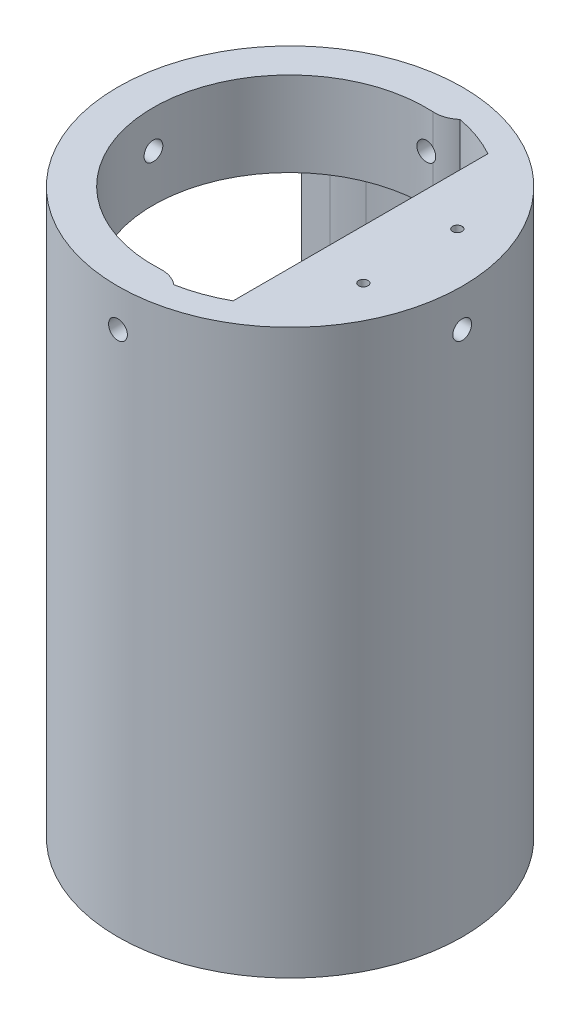
SolidWorks part; units mm, degrees
ref_plane "Front Plane" through (0, 0, 0) normal (0, 0, 1) x (1, 0, 0)
ref_plane "Top Plane" through (0, 0, 0) normal (0, 1, 0) x (1, 0, 0)
ref_plane "Right Plane" through (0, 0, 0) normal (1, 0, 0) x (0, 0, -1)
sketch "Sketch1" plane through (0, 0, 0) normal (0, 1, 0) x (1, 0, 0)
  circle A1 centre (0, 0) radius 46.609
  dimension "D1" = 93.218
extrude "Boss-Extrude1" add sketch "Sketch1" along normal blind 17.78
sketch "Sketch4" plane through (0, 17.78, 0) normal (0, 1, 0) x (1, 0, 0)
  line L0 (19.05, 42.5382) -> (19.05, -42.5382)
  circle A0 centre (0, 0) radius 46.609 construction
  arc A1 (19.05, 42.5382) -> (19.05, -42.5382) centre (0, 0) cw
  dimension "D1" = 19.05
extrude "Boss-Extrude2" add sketch "Sketch4" along normal blind 134.62
sketch "Sketch5" plane through (19.05, 0, 0) normal (-1, 0, 0) x (0, 0, 1)
  line L0 (-42.5382, 152.4) -> (42.5382, 152.4) construction
  line L1 (-26.67, 113.03) -> (26.67, 113.03)
  line L2 (-26.67, 113.03) -> (-26.67, 22.86)
  line L3 (-26.67, 22.86) -> (26.67, 22.86)
  line L4 (26.67, 113.03) -> (26.67, 22.86)
  line L5 (-25.879, 112.0381) -> (-25.4014, 113.03)
  line L6 (-25.4014, 113.03) -> (-25.879, 114.0219)
  line L7 (-25.879, 114.0219) -> (-26.9523, 114.2668)
  line L8 (-26.9523, 114.2668) -> (-27.813, 113.5804)
  line L9 (-27.813, 113.5804) -> (-27.813, 112.4796)
  line L10 (-27.813, 112.4796) -> (-26.9523, 111.7932)
  line L11 (-26.9523, 111.7932) -> (-25.879, 112.0381)
  line L12 (-42.5382, 17.78) -> (42.5382, 17.78) construction
  line L13 (27.9072, 113.03) -> (27.5448, 113.9048)
  line L14 (27.5448, 113.9048) -> (26.67, 114.2672)
  line L15 (26.67, 114.2672) -> (25.7952, 113.9048)
  line L16 (25.7952, 113.9048) -> (25.4328, 113.03)
  line L17 (25.4328, 113.03) -> (25.7952, 112.1552)
  line L18 (25.7952, 112.1552) -> (26.67, 111.7928)
  line L19 (26.67, 111.7928) -> (27.5448, 112.1552)
  line L20 (27.5448, 112.1552) -> (27.9072, 113.03)
  line L21 (-25.4328, 22.86) -> (-25.7952, 23.7348)
  line L22 (-25.7952, 23.7348) -> (-26.67, 24.0972)
  line L23 (-26.67, 24.0972) -> (-27.5448, 23.7348)
  line L24 (-27.5448, 23.7348) -> (-27.9072, 22.86)
  line L25 (-27.9072, 22.86) -> (-27.5448, 21.9852)
  line L26 (-27.5448, 21.9852) -> (-26.67, 21.6228)
  line L27 (-26.67, 21.6228) -> (-25.7952, 21.9852)
  line L28 (-25.7952, 21.9852) -> (-25.4328, 22.86)
  line L29 (27.9072, 22.86) -> (27.5448, 23.7348)
  line L30 (27.5448, 23.7348) -> (26.67, 24.0972)
  line L31 (26.67, 24.0972) -> (25.7952, 23.7348)
  line L32 (25.7952, 23.7348) -> (25.4328, 22.86)
  line L33 (25.4328, 22.86) -> (25.7952, 21.9852)
  line L34 (25.7952, 21.9852) -> (26.67, 21.6228)
  line L35 (26.67, 21.6228) -> (27.5448, 21.9852)
  line L36 (27.5448, 21.9852) -> (27.9072, 22.86)
  circle A4 centre (-26.67, 113.03) radius 1.143 construction
  circle A5 centre (26.67, 113.03) radius 1.143 construction
  circle A6 centre (-26.67, 22.86) radius 1.143 construction
  circle A7 centre (26.67, 22.86) radius 1.143 construction
  point P4 (0, 113.03)
  point P7 (0, 152.4)
  dimension "D5" = 2.286
  dimension "D6" = 2.286
  dimension "D7" = 2.286
  dimension "D8" = 2.286
  dimension "D1" = 0
  dimension "D2" = 5.08
  dimension "D3" = 90.17
  dimension "D4" = 53.34
sketch "Sketch9" plane through (0, 152.4, 0) normal (0, 1, 0) x (1, 0, 0)
  circle A0 centre (0, 0) radius 46.609
  circle A1 centre (0, 0) radius 39.37
  dimension "D1" = 93.218
  dimension "D2" = 78.74
extrude "Boss-Extrude5" add sketch "Sketch9" against normal up to surface (134.62 mm away) up to face at (-13.7795, 17.78, 0)
sketch "Sketch11" plane through (19.05, 0, 0) normal (-1, 0, 0) x (0, 0, 1)
  line L0 (-34.4542, 17.78) -> (-34.4542, 152.4) construction
  line L1 (-34.4542, 220.6179) -> (34.4542, 220.6179)
  line L2 (-34.4542, 220.6179) -> (-34.4542, 50.4379)
  line L3 (-34.4542, 50.4379) -> (34.4542, 50.4379)
  line L4 (34.4542, 220.6179) -> (34.4542, 50.4379)
  line L5 (34.4542, 152.4) -> (34.4542, 17.78) construction
  line L6 (-34.4542, 17.78) -> (34.4542, 17.78) construction
  line L7 (-34.4542, 154.94) -> (34.4542, 154.94)
  line L8 (-34.4542, 154.94) -> (-34.4542, 129.54)
  line L9 (-34.4542, 129.54) -> (34.4542, 129.54)
  line L10 (34.4542, 154.94) -> (34.4542, 129.54)
  line L12 (-34.4542, 50.4379) -> (34.4542, 50.4379)
  line L13 (-34.4542, 50.4379) -> (-34.4542, 17.78)
  line L14 (-34.4542, 17.78) -> (34.4542, 17.78)
  line L15 (34.4542, 50.4379) -> (34.4542, 17.78)
  line M13 (-34.4542, 152.4) -> (-34.4542, 17.78)
  line M15 (34.4542, 17.78) -> (34.4542, 152.4)
  dimension "D1" = 25.4
  dimension "D2" = 137.16
  dimension "D3" = 170.18
extrude "Cut-Extrude3" cut sketch "Sketch11" along normal blind 154.686 contours L7 L4 L1 M13 | L9 L3 M13 M15 | L13 L12 L15 L14 region at (19.05, 187.7789, 0) region at (19.05, 89.9889, 0)
sketch "Sketch12" plane through (19.05, 0, 0) normal (-1, 0, 0) x (0, 0, 1)
  line L0 (-34.4542, 17.78) -> (34.4542, 17.78) construction
  line L1 (-31.75, 147.32) -> (31.75, 147.32)
  line L2 (-31.75, 147.32) -> (-31.75, 121.92)
  line L3 (-31.75, 121.92) -> (31.75, 121.92)
  line L4 (31.75, 147.32) -> (31.75, 121.92)
  point P0 (0, 121.92)
  dimension "D1" = 25.4
  dimension "D2" = 0
  dimension "D3" = 63.5
  dimension "D4" = 104.14
sketch "Sketch13" plane through (0, 152.4, 0) normal (0, 1, 0) x (1, 0, 0)
  circle A0 centre (32.512, 0) radius 3.0803
  circle A1 centre (32.512, -12.7) radius 1.27
  circle A2 centre (32.512, 12.7) radius 1.27
  dimension "D4" = 2.54
  dimension "D5" = 2.54
  dimension "D1" = 12.7
  dimension "D2" = 12.7
  dimension "D3" = 0
  dimension "D6" = 32.512
extrude "Cut-Extrude4" cut sketch "Sketch13" against normal blind 12.7 contours A1 | A2
extrude "Cut-Extrude5" cut sketch "Sketch12" against normal blind 5.08
extrude "Cut-Extrude6" cut sketch "Sketch5" against normal blind 2.54 contours L35 L36 L29 L30 L4 L3 L33 L34 | L19 L20 L13 L14 L15 L16 L1 L4 | L17 L18 L4 L1 | L10 L11 L2 L1 L6 L7 L8 L9 | L2 L11 L5 L1 | L21 L22 L2 L3 | L27 L28 L3 L2 L23 L24 L25 L26 | L31 L32 L3 L4 | L22 L23 L24 L25 L26 L27 L28 L21 region at (19.05, 113.1938, -26.8374) region at (19.05, 112.5336, -26.1629) region at (19.05, 113.1959, 26.8359) region at (19.05, 112.5322, 26.1722) region at (19.05, 23.3578, -26.1722) region at (19.05, 22.6941, -26.8359) region at (19.05, 22.6941, 26.8359) region at (19.05, 23.3578, 26.1722)
fillet "Fillet1" radius 1.27 1 edges at (-46.609, 17.78, 0)
fillet "Fillet2" radius 20.32 2 edges at (-19.05, 73.66, -34.4542) (-19.05, 73.66, 34.4542)
sketch "Sketch16" plane through (0, 152.4, 0) normal (0, 1, 0) x (1, 0, 0)
  line L2 (7.24, 38.6986) -> (7.24, -38.6986)
  arc A0 (19.05, 34.4542) -> (19.05, -34.4542) centre (0, 0) ccw construction
  arc A1 (0, 39.37) -> (0, -39.37) centre (0, 0) ccw
  arc A2 (7.24, 36.1586) -> (7.24, -36.1586) centre (-0.1301, 0) ccw
  arc A3 (-15.6457, -36.1277) -> (19.05, -34.4542) centre (0, 0) ccw construction
  arc A4 (7.24, 38.6986) -> (7.24, -38.6986) centre (0, 0) ccw
  arc M3 (19.05, -34.4542) -> (19.05, 34.4542) centre (0, 0) cw
  dimension "D1" = 2.54
  dimension "D2" = 2.54
extrude "Boss-Extrude6" add sketch "Sketch16" against normal up to surface (22.86 mm away) contours M3 region at (6.325, 152.4, -37.4286) up to face at (-30.0474, 129.54, 0)
sketch "Sketch15" plane through (0, 0, 0) normal (0, 0, 1) x (1, 0, 0)
  line L0 (19.05, 152.4) -> (7.24, 152.4) construction
  circle A0 centre (0, 142.24) radius 2.54
  dimension "D1" = 5.08
  dimension "D2" = 10.16
extrude "Cut-Extrude8" cut sketch "Sketch15" against normal up to surface and the other way up to surface up to face at (-38.9993, 73.025, 0) other way up to face at (-38.9993, 73.025, 0)
sketch "Sketch14" plane through (0, 0, 0) normal (1, 0, 0) x (0, 0, -1)
  line L0 (38.6986, 152.4) -> (34.4542, 152.4) construction
  circle A0 centre (0, 142.24) radius 2.54
  dimension "D1" = 5.08
  dimension "D2" = 10.16
extrude "Cut-Extrude7" cut sketch "Sketch14" against normal up to surface and the other way up to surface up to face at (-2.4729, 142.82, -46.5434) other way up to face at (-2.4729, 142.82, -46.5434)
fillet "Fillet4" radius 7.62 2 edges at (7.24, 140.97, -36.1586) (7.24, 140.97, 36.1586)
